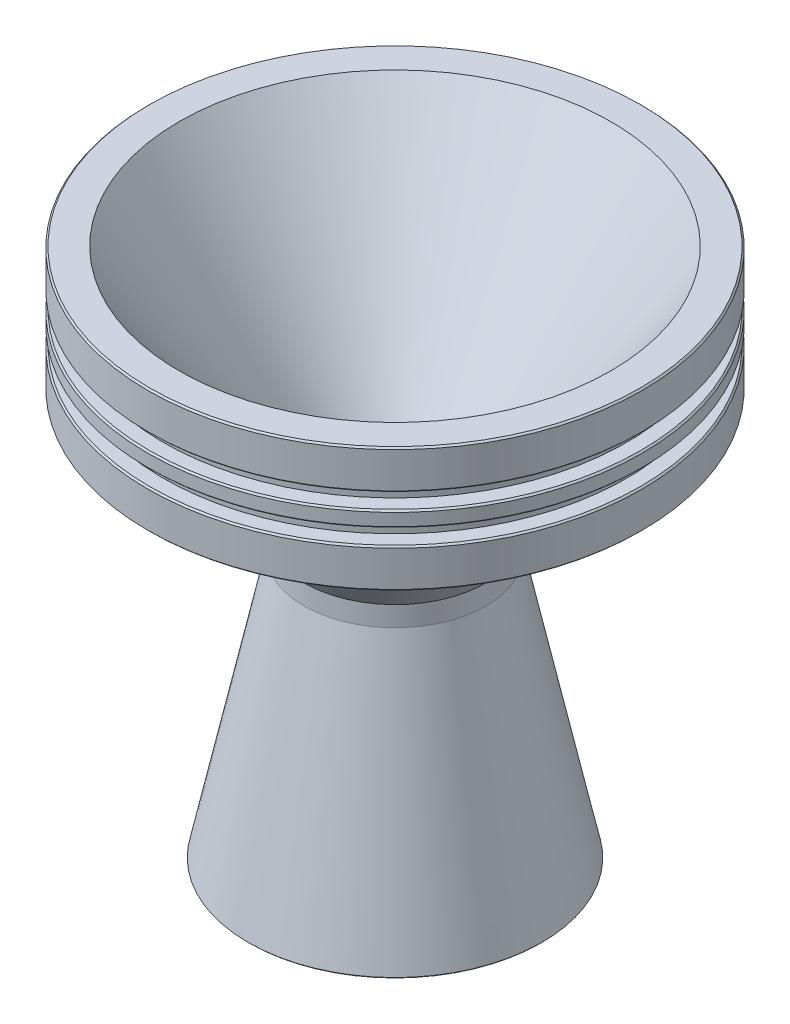
SolidWorks part; units mm, degrees
ref_plane "Front Plane" through (0, 0, 0) normal (0, 0, 1) x (1, 0, 0)
ref_plane "Top Plane" through (0, 0, 0) normal (0, 1, 0) x (1, 0, 0)
ref_plane "Right Plane" through (0, 0, 0) normal (1, 0, 0) x (0, 0, -1)
sketch "Sketch1" plane through (0, 0, 0) normal (0, 0, 1) x (1, 0, 0)
  line L0 (0, 0) -> (2.54, 0)
  line L8 (0, 0) -> (0, -3.175)
  line L9 (0, -3.175) -> (1.27, -3.175)
  line L10 (1.27, -3.175) -> (1.27, -4.445)
  line L11 (1.27, -4.445) -> (0, -4.445)
  line L12 (0, -4.445) -> (0, -5.715)
  line L13 (0, -5.715) -> (1.27, -5.715)
  line L14 (1.27, -5.715) -> (1.27, -6.985)
  line L15 (1.27, -6.985) -> (0, -6.985)
  line L16 (0, -6.985) -> (0, -10.16)
  line L18 (0, 0) -> (20.193, 0) construction
  line L19 (20.193, 0) -> (20.193, -43.3999) construction
  line L20 (2.54, 0) -> (16.002, -19.2257)
  line L22 (11.4035, -43.3999) -> (8.1576, -43.3999)
  line L24 (16.002, -19.2257) -> (16.002, -21.7657)
  line L25 (16.002, -21.7657) -> (11.4035, -43.3999)
  line L27 (20.193, -43.3999) -> (11.4035, -43.3999) construction
  line L29 (5.7781, -10.16) -> (0, -10.16)
  line L30 (12.7561, -21.7657) -> (16.002, -21.7657) construction
  line L33 (12.7561, -20.1255) -> (5.7781, -10.16)
  line L34 (12.7561, -21.7657) -> (8.1576, -43.3999)
  line L35 (12.7561, -20.1255) -> (12.7561, -21.7657)
  line L36 (12.7561, -20.1255) -> (16.002, -19.2257) construction
  dimension "D1" = 2.54
  dimension "D2" = 1.27
  dimension "D3" = 1.27
  dimension "D4" = 3.175
  dimension "D5" = 1.27
  dimension "D6" = 20.193
  dimension "D7" = 2.54
  dimension "D8" = 35
  dimension "D9" = 12
  dimension "D10" = 3.175
  dimension "D11" = 4.191
  dimension "D12" = 3.175
  dimension "D13" = 3.175
  dimension "D14" = 43.3999
revolve "base_revolve" add sketch "Sketch1" angle 360 about L19
chamfer "outer_chamfers" distance 0.127 angle 45 7 edges at (0, -10.16, 0) (0, 0, 0) (8.1576, -43.3999, 0) (0, -5.715, 0) (0, -6.985, 0) (0, -4.445, 0) (0, -3.175, 0) first distance on face at (5.7781, -10.16, 0) first distance on face at (0, -3.175, 0) first distance on face at (11.4035, -43.3999, 0) first distance on face at (1.27, -5.715, 0) first distance on face at (0, -6.985, 0) first distance on face at (0, -5.715, 0) first distance on face at (1.27, -3.175, 0)
